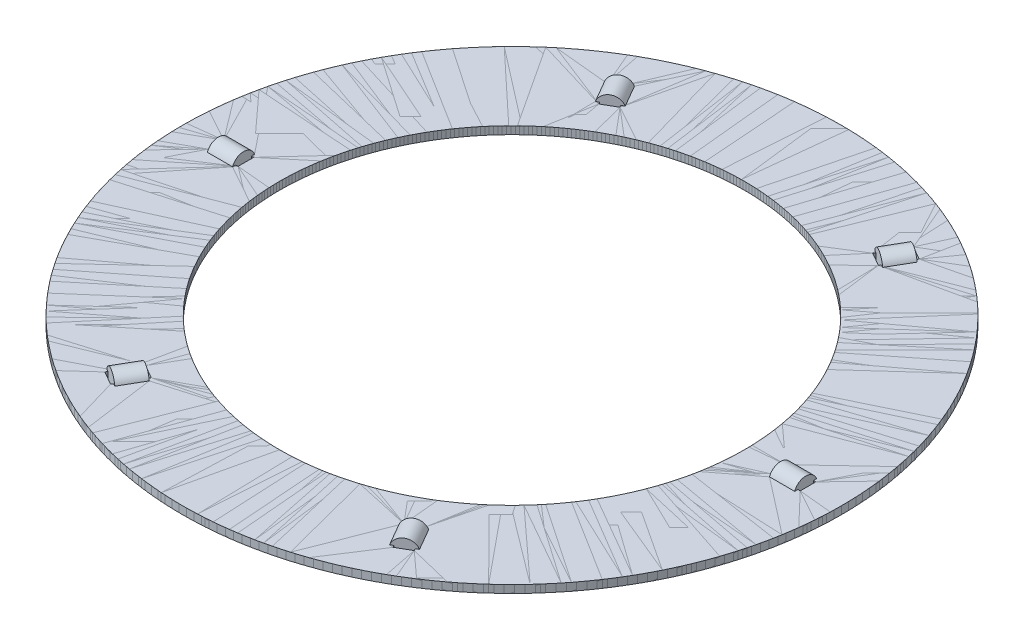
SolidWorks part; units mm, degrees
ref_plane "前视基准面" through (0, 0, 0) normal (0, 0, 1) x (1, 0, 0)
ref_plane "上视基准面" through (0, 0, 0) normal (0, 1, 0) x (1, 0, 0)
ref_plane "右视基准面" through (0, 0, 0) normal (1, 0, 0) x (0, 0, -1)
sketch "草图1" plane through (0, 0, 0) normal (0, 0, 1) x (1, 0, 0)
  line L0 (0, 87.2061) -> (0, -91.5733) construction
  line L1 (-94.3327, 0) -> (80.3525, 0) construction
  line L2 (-30, 0.5) -> (-30, -0.5)
  line L3 (-42.5, 0.5) -> (-30, 0.5)
  line L4 (-42.5, 0.5) -> (-42.5, -0.5)
  line L5 (-42.5, -0.5) -> (42.5, -0.5)
  line L6 (42.5, 0.5) -> (42.5, -0.5)
  line L7 (-37.875, 1.5) -> (-34.625, 1.5)
  line L8 (-34.625, 1.5) -> (-34.625, -1.5)
  line L9 (-34.625, -1.5) -> (-37.875, -1.5)
  line L10 (-37.875, -1.5) -> (-37.875, 1.5)
  line L11 (0, 0.5) -> (42.5, 0.5)
  line L12 (-36.25, 0.5) -> (-36.25, -4.4473) construction
  dimension "D1" = 1
  dimension "（Dc）" = 85
  dimension "D2" = 3.25
  dimension "dc" = 60
  dimension "Dw" = 3
sketch "草图2" plane through (0, 0, 0) normal (0, 0, 1) x (1, 0, 0)
  line L0 (-37.875, 1.5) -> (-34.625, 1.5) construction
  line L1 (-34.625, 1.5) -> (-34.625, -1.5) construction
  line L2 (-34.625, -1.5) -> (-37.875, -1.5) construction
  line L3 (-37.875, -1.5) -> (-37.875, 1.5) construction
  line L4 (-30, 0.5) -> (-30, -0.5) construction
  line L5 (-42.5, 0.5) -> (-30, 0.5) construction
  line L6 (-42.5, 0.5) -> (-42.5, -0.5) construction
  line L7 (-42.5, -0.5) -> (42.5, -0.5) construction
  line L8 (42.5, 0.5) -> (42.5, -0.5) construction
  line L9 (0, 0.5) -> (42.5, 0.5) construction
  line L10 (-37.875, 1.5) -> (-34.625, 1.5)
  line L11 (-34.625, 1.5) -> (-34.625, -1.5)
  line L12 (-34.625, -1.5) -> (-37.875, -1.5)
  line L13 (-37.875, -1.5) -> (-37.875, 1.5)
  line L14 (-30, 0.5) -> (-30, -0.5)
  line L15 (-42.5, 0.5) -> (-30, 0.5)
  line L16 (-42.5, 0.5) -> (-42.5, -0.5)
  line L17 (-42.5, -0.5) -> (42.5, -0.5)
  line L18 (42.5, 0.5) -> (42.5, -0.5)
  line L19 (0, 0.5) -> (42.5, 0.5)
  line L20 (-37.875, 0) -> (-34.625, 0)
revolve "旋转1" add sketch "草图2" angle 360 about L0 region at (-36.25, 0.25, 0) region at (-40.1875, 0, 0) region at (-32.3125, 0, 0) region at (-36.25, -0.25, 0)
sketch "草图3" plane through (0, 0, 0) normal (0, 0, 1) x (1, 0, 0)
  line L1 (-38.175, 1.5) -> (-34.325, 1.5)
  line L2 (-38.175, 1.5) -> (-38.175, -1.5)
  line L3 (-38.175, -1.5) -> (-34.325, -1.5) construction
  line L4 (-34.325, 1.5) -> (-34.325, -1.5)
  line L5 (-34.325, -1.5) -> (-38.175, -1.5)
  line L6 (-37.875, -1.5) -> (-37.875, 1.5) construction
  line L7 (-34.625, 1.5) -> (-34.625, -1.5) construction
  dimension "D1" = 0.3
  dimension "D2" = 0.3
extrude "切除-拉伸2" cut sketch "草图3" against normal mid plane 2
pattern_circular "阵列(圆周)1" count 6 over 360 about axis through (0, 87.2061, 0) along (0, 1, 0) of "切除-拉伸2"
revolve "旋转5" add sketch "草图2<6>" angle 360 about L1 region at (-36.25, 1, 0) region at (-36.25, 0.25, 0)
sketch "草图2<6>" plane through (0, 0, 0) normal (0, 0, 1) x (1, 0, 0) same geometry as "草图2"
pattern_circular "阵列(圆周)2" count 6 over 360 about axis through (0, 87.2061, 0) along (0, 1, 0) of bodies 102
